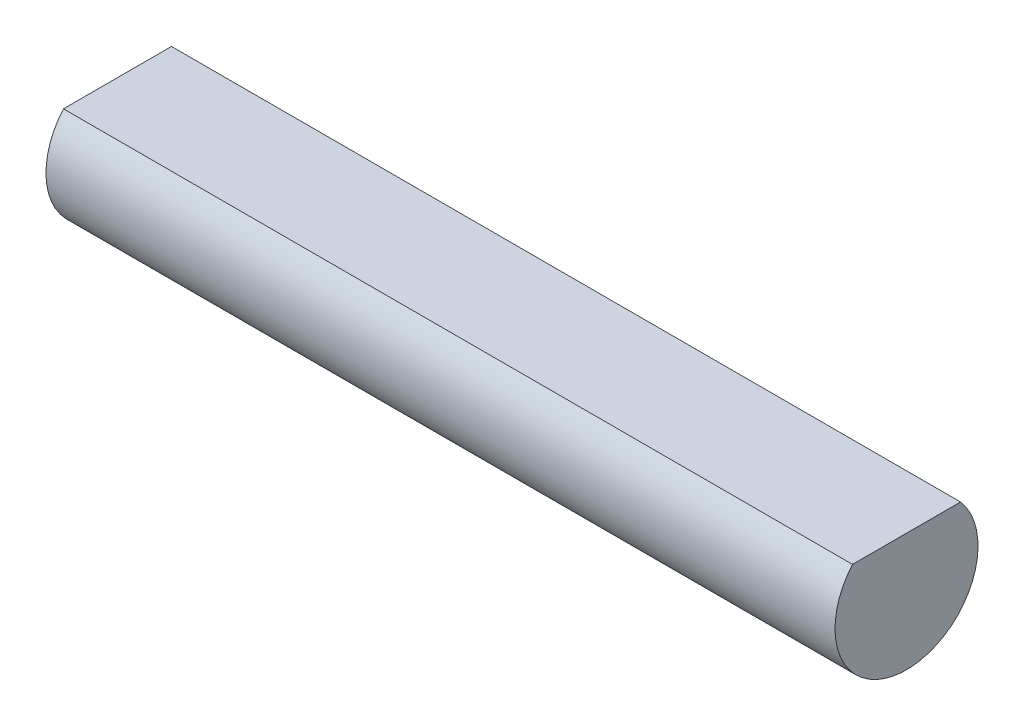
SolidWorks part; units mm, degrees
ref_plane "Front Plane" through (0, 0, 0) normal (0, 0, 1) x (1, 0, 0)
ref_plane "Top Plane" through (0, 0, 0) normal (0, 1, 0) x (1, 0, 0)
ref_plane "Right Plane" through (0, 0, 0) normal (1, 0, 0) x (0, 0, -1)
sketch "Sketch1" plane through (0, 0, 0) normal (1, 0, 0) x (0, 0, -1)
  line L0 (0, -1.5) -> (0, 1)
  line L1 (0, 1) -> (-1.118, 1)
  line L2 (-1.118, 1) -> (1.118, 1)
  line L3 (-1.0954, 0.95) -> (1.0954, 0.95)
  arc A0 (-1.118, 1) -> (1.118, 1) centre (0, 0) ccw
  arc A1 (-1.0954, 0.95) -> (1.0954, 0.95) centre (0, 0) ccw
  dimension "D1" = 3
  dimension "D2" = 2.5
  dimension "D3" = 0.05
extrude "Boss-Extrude1" add sketch "Sketch1" along normal blind 8 and the other way blind 8 contours L3 A1 L0 | L0 A1 L3 region at (0, -0.1499, 0.6405) region at (0, -0.1499, -0.6405)
